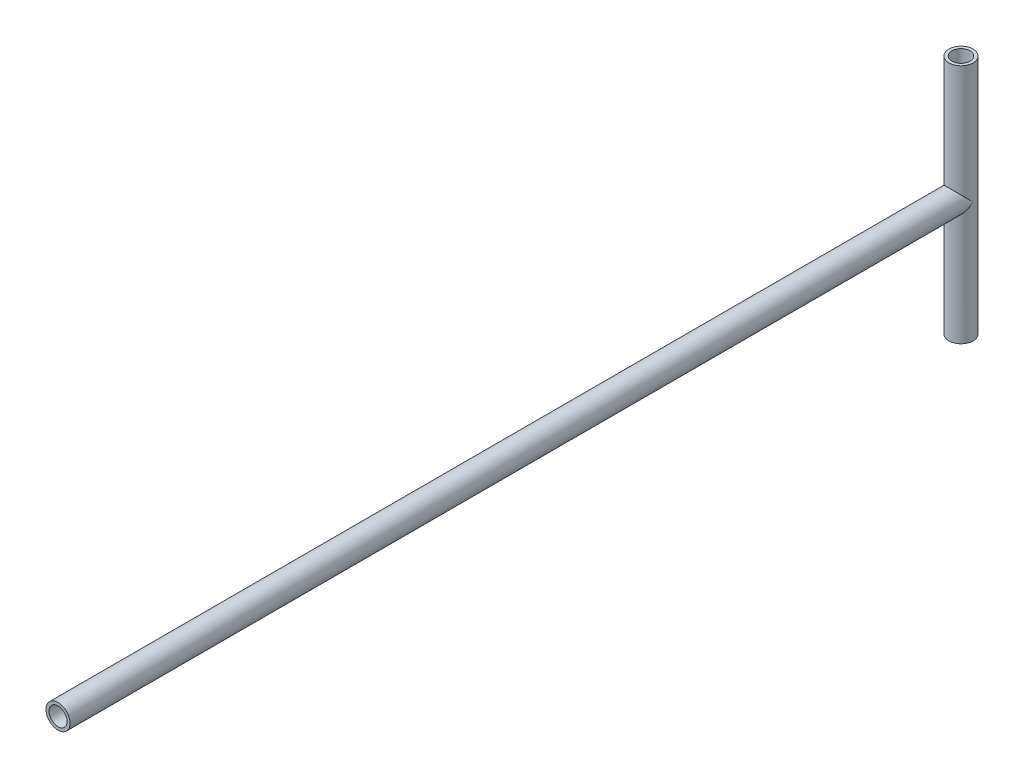
SolidWorks part; units mm, degrees
ref_plane "Front Plane" through (0, 0, 0) normal (0, 0, 1) x (1, 0, 0)
ref_plane "Top Plane" through (0, 0, 0) normal (0, 1, 0) x (1, 0, 0)
ref_plane "Right Plane" through (0, 0, 0) normal (1, 0, 0) x (0, 0, -1)
sketch "Sketch3" plane through (0, 0, 0) normal (0, 0, 1) x (1, 0, 0)
  circle A0 centre (0, 0) radius 4
  circle A1 centre (0, 0) radius 3
  dimension "D1" = 8
  dimension "D2" = 6
extrude "Boss-Extrude1" add sketch "Sketch3" along normal blind 300
sketch "Sketch6" plane through (0, 0, 0) normal (0, 1, 0) x (1, 0, 0)
  circle A0 centre (0, 0) radius 4
  circle A1 centre (0, 0) radius 3
  dimension "D1" = 8
  dimension "D2" = 6
extrude "Boss-Extrude3" add sketch "Sketch6" along normal blind 40 and the other way blind 40 contours A0 | A1
sketch "Sketch7" plane through (0, -40, 0) normal (0, -1, 0) x (1, 0, 0)
  circle A0 centre (0, 0) radius 3
extrude "Cut-Extrude1" cut sketch "Sketch7" against normal through all both and the other way through all
